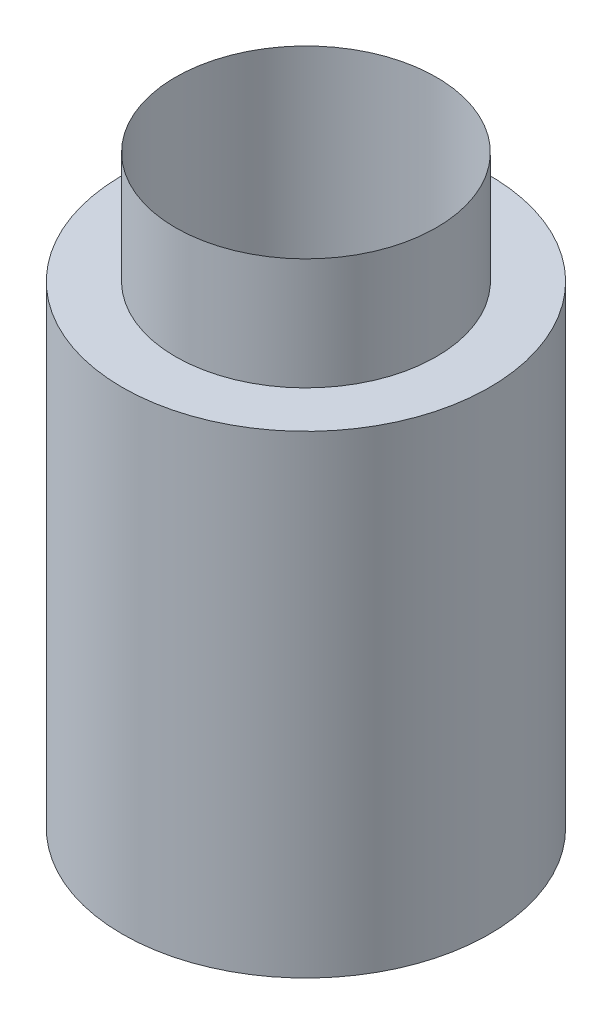
SolidWorks part; units mm, degrees
ref_plane "Front Plane" through (0, 0, 0) normal (0, 0, 1) x (1, 0, 0)
ref_plane "Top Plane" through (0, 0, 0) normal (0, 1, 0) x (1, 0, 0)
ref_plane "Right Plane" through (0, 0, 0) normal (1, 0, 0) x (0, 0, -1)
sketch "Sketch1" plane through (0, 0, 0) normal (0, 1, 0) x (1, 0, 0)
  circle A0 centre (0, 0) radius 34.5164
  circle A1 centre (0, 0) radius 24.5164
  circle A2 centre (0, 0) radius 23.5164
  dimension "D1" = 10
  dimension "D2" = 1
extrude "Boss-Extrude2" add sketch "Sketch1" along normal blind 89 contours A0 A1 region at (-33.5401, 0, 0)
surface "Surface-Extrude2" sketch "Sketch1<7>" parameters "D1"=110
sketch "Sketch1<7>" plane through (0, 0, 0) normal (0, 1, 0) x (1, 0, 0) same geometry as "Sketch1"
